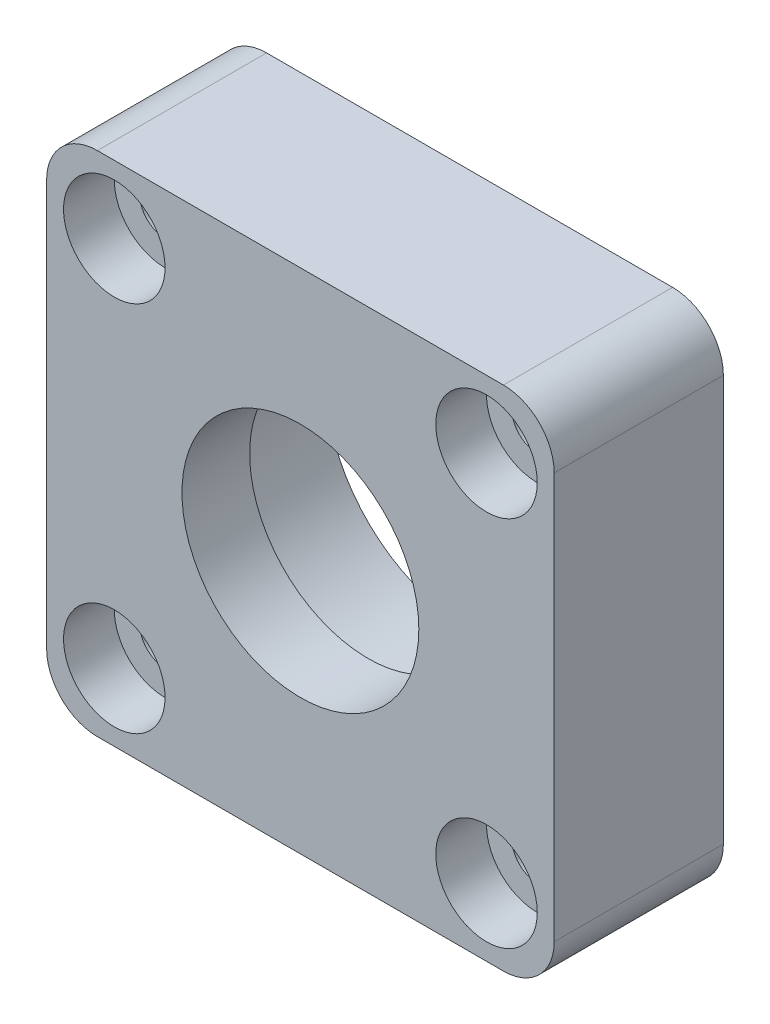
SolidWorks part; units mm, degrees
ref_plane "Front Plane" through (0, 0, 0) normal (0, 0, 1) x (1, 0, 0)
ref_plane "Top Plane" through (0, 0, 0) normal (0, 1, 0) x (1, 0, 0)
ref_plane "Right Plane" through (0, 0, 0) normal (1, 0, 0) x (0, 0, -1)
sketch "Sketch1" plane through (0, 0, 0) normal (0, 0, 1) x (1, 0, 0)
  line L1 (-15, -15) -> (15, -15)
  line L2 (-15, -15) -> (-15, 15)
  line L3 (-15, 15) -> (15, 15)
  line L4 (15, -15) -> (15, 15)
  line L5 (-15, -15) -> (15, 15) construction
  line L6 (-15, 15) -> (15, -15) construction
  circle A0 centre (0, 0) radius 7
  point P0 (0, 0)
  dimension "D3" = 14
  dimension "D1" = 30
  dimension "D2" = 30
extrude "Boss-Extrude1" add sketch "Sketch1" along normal blind 10
sketch "Sketch2" plane through (0, 0, 0) normal (0, 0, 1) x (1, 0, 0)
  circle A0 centre (0, 0) radius 8.5
  dimension "D1" = 17
extrude "Cut-Extrude1" cut sketch "Sketch2" along normal blind 6
sketch "Sketch3" plane through (0, 0, 10) normal (0, 0, 1) x (1, 0, 0)
  line L1 (-11, -11) -> (11, -11) construction
  line L2 (-11, -11) -> (-11, 11) construction
  line L3 (-11, 11) -> (11, 11) construction
  line L4 (11, -11) -> (11, 11) construction
  line L5 (-11, -11) -> (11, 11) construction
  line L6 (-11, 11) -> (11, -11) construction
  circle A0 centre (-11, 11) radius 1.5
  circle A1 centre (11, 11) radius 1.5
  circle A2 centre (11, -11) radius 1.5
  circle A3 centre (-11, -11) radius 1.5
  point P0 (0, 0)
  dimension "D3" = 3
  dimension "D4" = 3
  dimension "D5" = 3
  dimension "D6" = 3
  dimension "D1" = 22
  dimension "D2" = 22
extrude "Cut-Extrude2" cut sketch "Sketch3" against normal through all
sketch "Sketch4" plane through (0, 0, 10) normal (0, 0, 1) x (1, 0, 0)
  circle A0 centre (-11, 11) radius 3
  circle A1 centre (11, 11) radius 3
  circle A2 centre (11, -11) radius 3
  circle A3 centre (-11, -11) radius 3
  dimension "D1" = 6
  dimension "D2" = 6
  dimension "D3" = 6
  dimension "D4" = 6
extrude "Cut-Extrude3" cut sketch "Sketch4" against normal blind 3
fillet "Fillet1" radius 3 4 edges at (-15, -15, 5) (15, -15, 5) (15, 15, 5) (-15, 15, 5)
